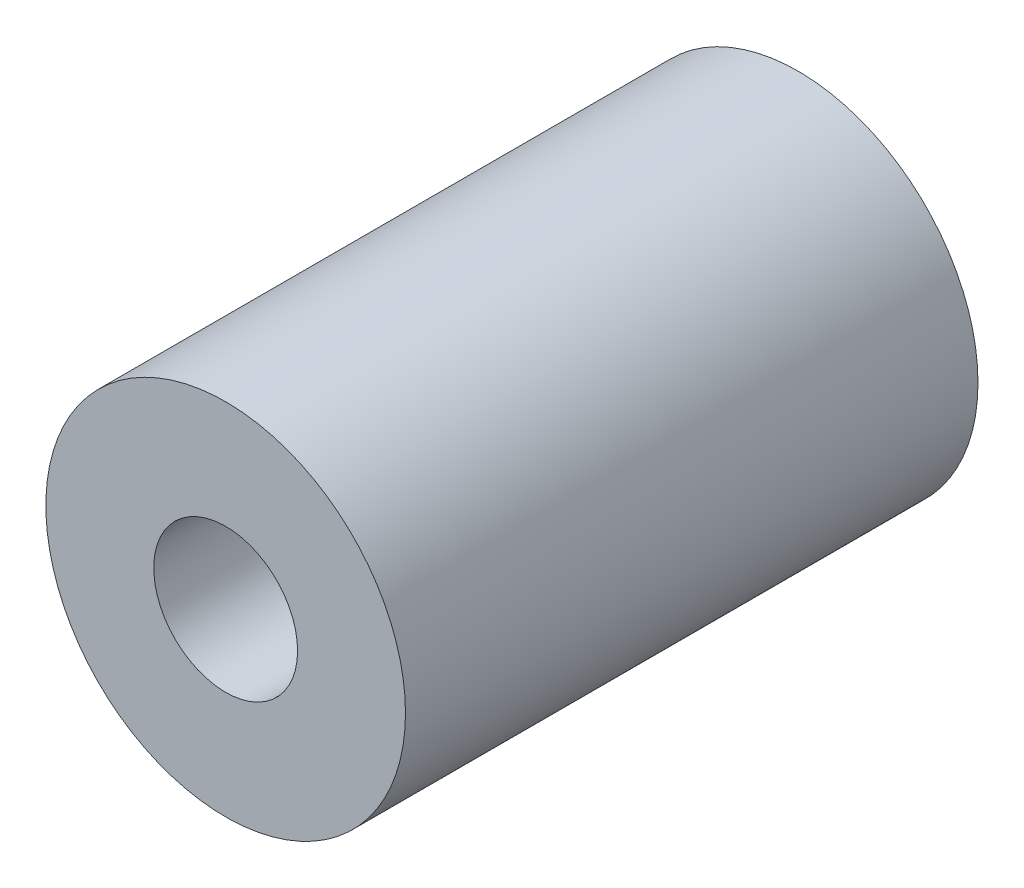
SolidWorks part; units mm, degrees
material "ABS"
ref_plane "Front Plane" through (0, 0, 0) normal (0, 0, 1) x (1, 0, 0)
ref_plane "Top Plane" through (0, 0, 0) normal (0, 1, 0) x (1, 0, 0)
ref_plane "Right Plane" through (0, 0, 0) normal (1, 0, 0) x (0, 0, -1)
sketch "Sketch1" plane through (0, 0, 0) normal (0, 0, 1) x (1, 0, 0)
  circle A0 centre (0, 0) radius 1.27
  circle A1 centre (0, 0) radius 3.175
  dimension "D1" = 2.54
  dimension "D2" = 6.35
extrude "Boss-Extrude1" add sketch "Sketch1" along normal blind 10.1092
